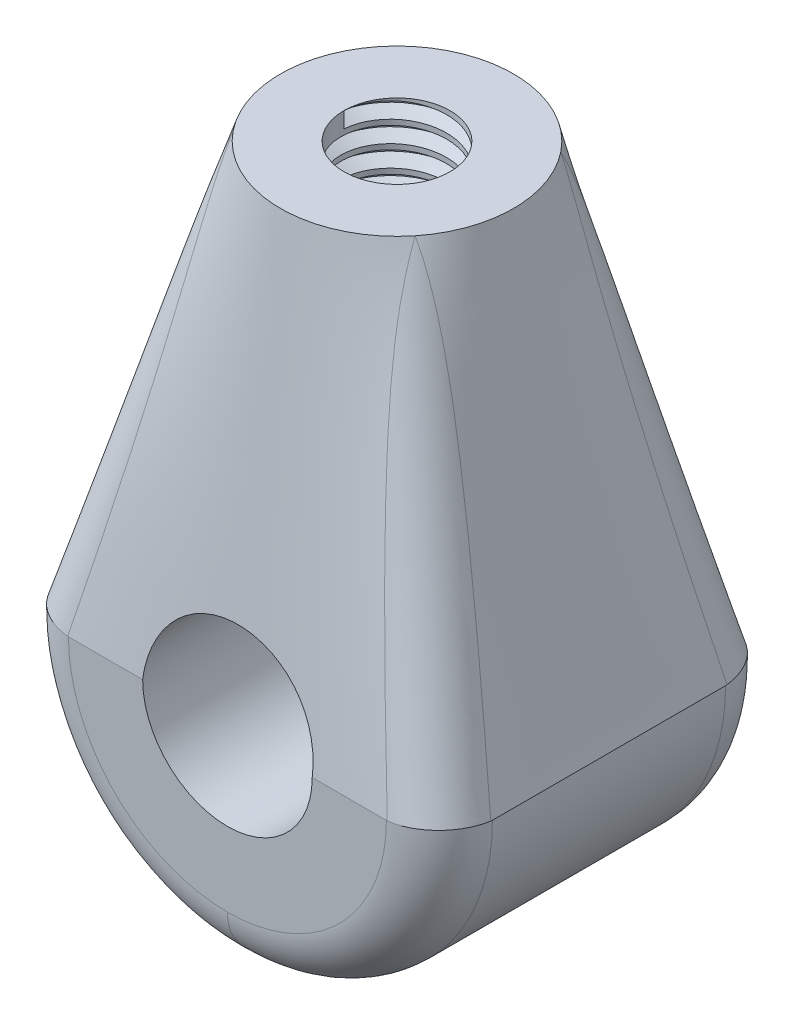
SolidWorks part; units mm, degrees
ref_plane "Front Plane" through (0, 0, 0) normal (0, 0, 1) x (1, 0, 0)
ref_plane "Top Plane" through (0, 0, 0) normal (0, 1, 0) x (1, 0, 0)
ref_plane "Right Plane" through (0, 0, 0) normal (1, 0, 0) x (0, 0, -1)
sketch "Sketch2" plane through (0, 0, 0) normal (0, 1, 0) x (1, 0, 0)
  line L1 (-10, -8) -> (10, -8)
  line L2 (-10, -8) -> (-10, 8)
  line L3 (-10, 8) -> (10, 8)
  line L4 (10, -8) -> (10, 8)
  line L5 (-10, -8) -> (10, 8) construction
  line L6 (-10, 8) -> (10, -8) construction
  point P0 (0, 0)
  dimension "D1" = 20
  dimension "D2" = 16
ref_plane "Plane1" through (0, 20, 0) normal (0, 1, 0) x (1, 0, 0)
sketch "Sketch3" plane through (0, 20, 0) normal (0, 1, 0) x (1, 0, 0)
  circle A0 centre (0, 0) radius 5.5
  dimension "D1" = 11
loft "Loft1" add profiles "Sketch2", "Sketch3" connector at (-10, 0, -8) connector at (0.0449, 20, -5.4998)
sketch "Sketch4" plane through (0, 0, 0) normal (0, -1, 0) x (1, 0, 0)
  line L4 (10, -8) -> (10, 8)
  line L5 (10, 8) -> (-10, 8)
  line L6 (-10, 8) -> (-10, -8)
  line L7 (-10, -8) -> (10, -8)
  line L8 (10, -8) -> (10, 8)
  line L9 (10, 8) -> (-10, 8)
  line L10 (-10, 8) -> (-10, -8)
  line L11 (-10, -8) -> (10, -8)
  dimension "D1" = 0
extrude "Boss-Extrude1" add sketch "Sketch4" along normal blind 10
sketch "Sketch5" plane through (0, 0, -8) normal (0, 0, -1) x (-1, 0, 0)
  line L0 (-10, 0) -> (10, 0) construction
  circle A0 centre (0, 0) radius 4
  dimension "D1" = 8
extrude "Cut-Extrude1" cut sketch "Sketch5" against normal blind 16
sketch "Sketch6" plane through (0, 20, 0) normal (0, 1, 0) x (1, 0, 0)
  circle A0 centre (0, 0) radius 2.5
  dimension "D1" = 5
extrude "Cut-Extrude2" cut sketch "Sketch6" against normal blind 10
fillet "Fillet1" radius 10 2 edges at (-10, -10, 0) (10, -10, 0)
fillet "Fillet2" radius 2.5 8 edges
thread "Thread1" pitch 1 method cut profile "Thread Profile1" start angle 0, offset 0, length 0, pitch 1, diameter 5
ref_plane "Plane2" through (-2.5, 20, 0) normal (0, 0, 1) x (-1, 0, 0)
sketch "Thread Profile1" plane through (-2.5, 20, 0) normal (0, 0, 1) x (-1, 0, 0)
  line L0 (0, 0) -> (0, 1) construction
  line L1 (0, 0) -> (0.5413, 0.3125)
  line L2 (0.5413, 0.3125) -> (0.5413, 0.4375)
  line L3 (0.5413, 0.4375) -> (0, 0.75)
  line L4 (0.5413, 0.375) -> (0, 0.375) construction
  line L11 (0, 0) -> (0, 0.75)
  point P2 (0, 0)
  dimension "Pitch" = 1
  dimension "Profile_Angle" = 60
  dimension "Profile_Land" = 0.125
  dimension "Profile_Height" = 0.5413
